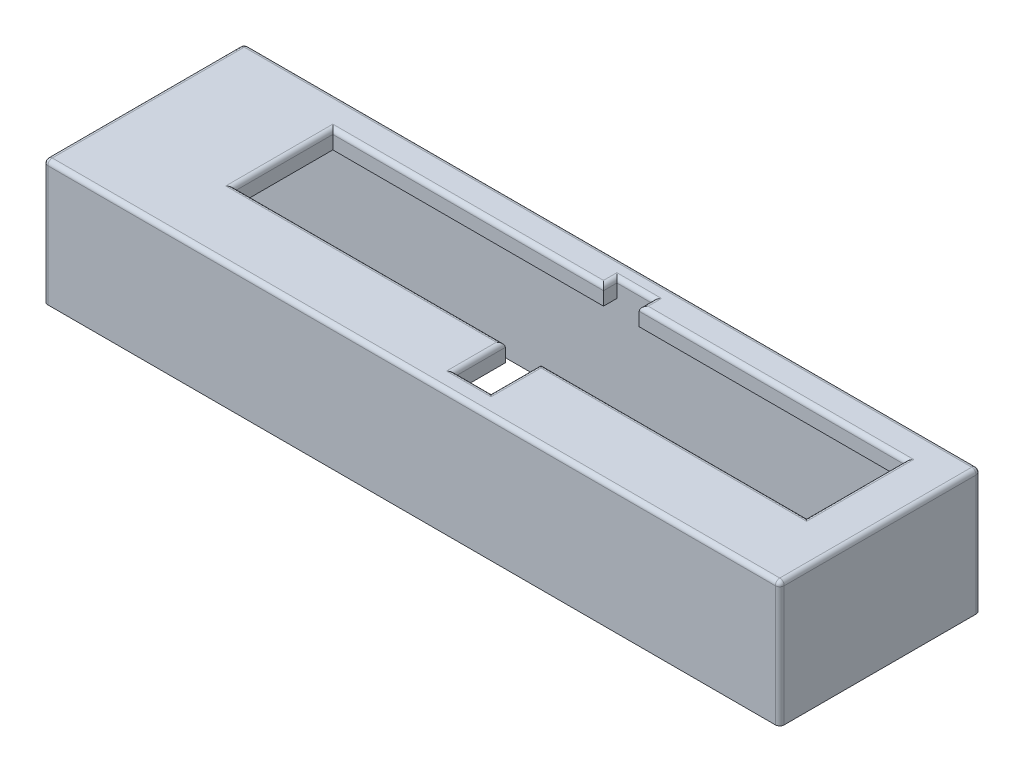
SolidWorks part; units mm, degrees
ref_plane "Front" through (0, 0, 0) normal (0, 0, 1) x (1, 0, 0)
ref_plane "Top" through (0, 0, 0) normal (0, 1, 0) x (1, 0, 0)
ref_plane "Right" through (0, 0, 0) normal (1, 0, 0) x (0, 0, -1)
sketch "Sketch1" plane through (0, 0, 0) normal (0, 1, 0) x (1, 0, 0)
  line L1 (-104.775, 22.86) -> (104.775, 22.86)
  line L2 (-104.775, 22.86) -> (-104.775, -34.29)
  line L3 (-104.775, -34.29) -> (104.775, -34.29)
  line L4 (104.775, 22.86) -> (104.775, -34.29)
  line L7 (-55, 0) -> (55, 0) construction
  point P0 (0, 0)
  dimension "D1" = 209.55
  dimension "D2" = 22.86
  dimension "D3" = 34.29
extrude "Boss-Extrude1" add sketch "Sketch1" along normal blind 5.08
sketch "Sketch2" plane through (0, 0, 0) normal (0, -1, 0) x (1, 0, 0)
  line L1 (-99.695, 29.21) -> (99.695, 29.21)
  line L2 (-99.695, 29.21) -> (-99.695, -17.78)
  line L3 (-99.695, -17.78) -> (99.695, -17.78)
  line L4 (99.695, 29.21) -> (99.695, -17.78)
  line L10 (104.775, -22.86) -> (104.775, 34.29)
  line L11 (104.775, 34.29) -> (-104.775, 34.29)
  line L12 (-104.775, 34.29) -> (-104.775, -22.86)
  line L13 (-104.775, -22.86) -> (104.775, -22.86)
  line L14 (104.775, -22.86) -> (104.775, 34.29)
  line L15 (104.775, 34.29) -> (-104.775, 34.29)
  line L16 (-104.775, 34.29) -> (-104.775, -22.86)
  line L17 (-104.775, -22.86) -> (104.775, -22.86)
  point P0 (0, 0)
  dimension "D2" = 5.08
  dimension "D3" = 5.08
  dimension "D4" = 5.08
  dimension "D1" = 0
extrude "Boss-Extrude2" add sketch "Sketch2" along normal blind 30.48 contours L14 L15 L16 L17 | L2 L1 L4 L3
sketch "Sketch3" plane through (0, 5.08, 0) normal (0, 1, 0) x (1, 0, 0)
  line L0 (104.775, 22.86) -> (-104.775, 22.86) construction
  line L1 (-92.0869, 13.97) -> (92.0869, 13.97)
  line L2 (-92.0869, 13.97) -> (-92.0869, -13.97)
  line L3 (-92.0869, -13.97) -> (92.0869, -13.97)
  line L4 (92.0869, 13.97) -> (92.0869, -13.97)
  line L5 (-92.0869, 13.97) -> (92.0869, -13.97) construction
  line L6 (-92.0869, -13.97) -> (92.0869, 13.97) construction
  line L7 (-70.6685, 13.97) -> (-70.6685, -13.97)
  line L13 (6.35, -13.97) -> (16.51, -13.97)
  line L18 (0, -19.558) -> (0, 19.558) construction
  line L19 (6.35, 13.97) -> (16.51, 13.97)
  line L20 (6.35, 13.97) -> (6.35, 17.78)
  line L21 (6.35, 17.78) -> (16.51, 17.78)
  line L22 (16.51, 13.97) -> (16.51, 17.78)
  line L28 (6.35, -13.97) -> (6.35, -28.179)
  line L29 (6.35, -28.179) -> (16.51, -28.179)
  line L30 (16.51, -13.97) -> (16.51, -28.179)
  point P0 (0, 0)
  dimension "D1" = 8.89
  dimension "D2" = 10.16
  dimension "D3" = 3.81
  dimension "D4" = 6.35
extrude "Cut-Extrude2" cut sketch "Sketch3" against normal up to next contours L1 L7 L3 L4 | L30 L29 L28 L13 | L21 L22 L19 L20 region at (10.7092, 5.08, 0)
fillet "Fillet1" radius 1.27 20 edges at (0, 5.08, 34.29) (-104.775, 5.08, 5.715) (0, 5.08, -22.86) (104.775, 5.08, 5.715) (11.43, 5.08, 28.179) (16.51, 5.08, 21.0745) (54.2985, 5.08, 13.97) (92.0869, 5.08, 0) (54.2985, 5.08, -13.97) (16.51, 5.08, -15.875) (11.43, 5.08, -17.78) (6.35, 5.08, -15.875) (-32.1593, 5.08, -13.97) (-70.6685, 5.08, 0) (-32.1593, 5.08, 13.97) (6.35, 5.08, 21.0745) (104.775, -12.7, 34.29) (104.775, -12.7, -22.86) (-104.775, -12.7, 34.29) (-104.775, -12.7, -22.86)
